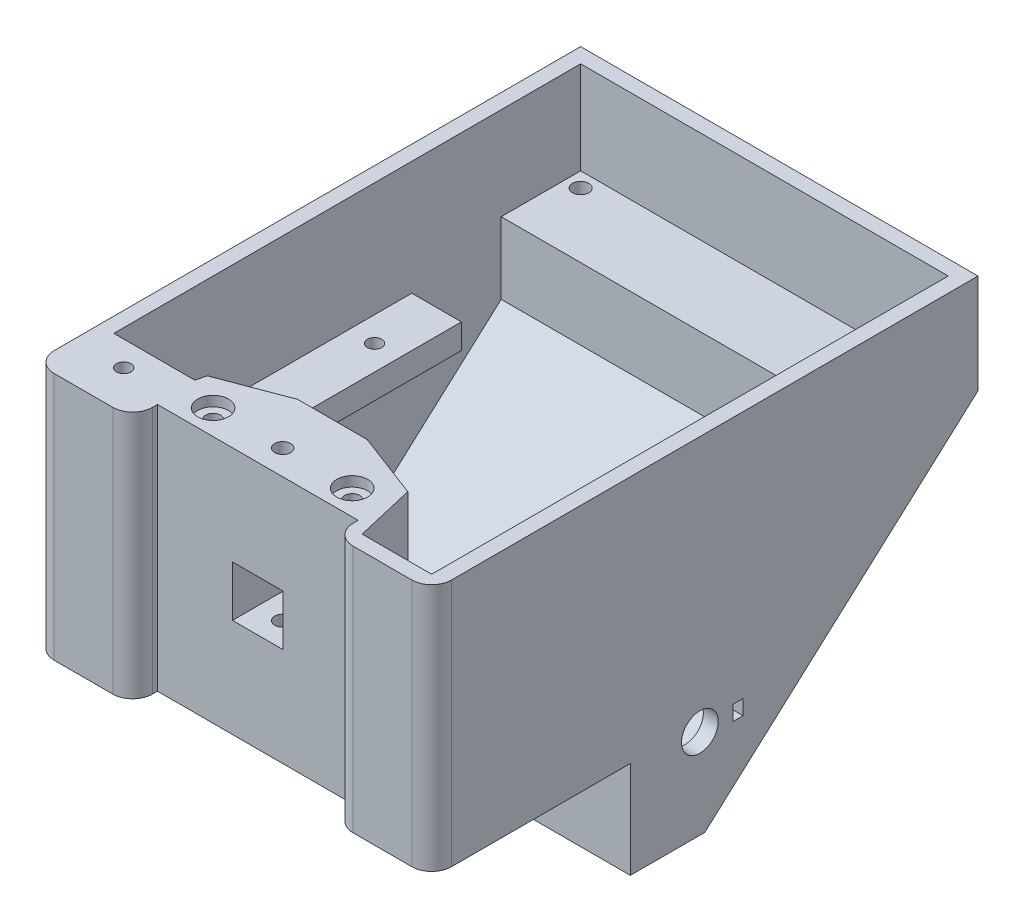
SolidWorks part; units mm, degrees
ref_plane "Спереди" through (0, 0, 0) normal (0, 0, 1) x (1, 0, 0)
ref_plane "Сверху" through (0, 0, 0) normal (0, 1, 0) x (1, 0, 0)
ref_plane "Справа" through (0, 0, 0) normal (1, 0, 0) x (0, 0, -1)
sketch "Sketch2" plane through (0, 0, 0) normal (1, 0, 0) x (0, 0, -1)
  line L0 (-27.3205, 20.9982) -> (-27.3205, -29.0018)
  line L1 (-27.3205, -29.0018) -> (12.6795, -29.0018)
  line L2 (12.6795, -29.0018) -> (12.6795, -48.5114)
  line L3 (12.6795, -48.5114) -> (27.6795, -48.5114)
  line L4 (82.6795, 20.9982) -> (82.6795, 0.9982)
  line L5 (82.6795, 20.9982) -> (-27.3205, 20.9982)
  line L6 (82.6795, 0.9982) -> (27.6795, -48.5114)
  dimension "D1" = 110
  dimension "D2" = 50
  dimension "D3" = 40
  dimension "D4" = 15
  dimension "D5" = 20
extrude "Boss-Extrude1" add sketch "Sketch2" along normal blind 80
shell "Shell1" thickness 3 removed face at (40, 20.9982, -27.6795)
sketch "Sketch3" plane through (0, 0, 24.3205) normal (0, 0, -1) x (-1, 0, 0)
  line L0 (-40, 20.9982) -> (-40, -26.0018) construction
  line L3 (-77, 20.9982) -> (-3, 20.9982) construction
  line L4 (-77, -26.0018) -> (-3, -26.0018) construction
  line L6 (-17, 20.9982) -> (-63, 20.9982)
  line L7 (-17, 20.9982) -> (-17, -26.0018)
  line L8 (-17, -26.0018) -> (-63, -26.0018)
  line L9 (-63, 20.9982) -> (-63, -26.0018)
  line L10 (-17, 20.9982) -> (-63, -26.0018) construction
  line L11 (-17, -26.0018) -> (-63, 20.9982) construction
  point P6 (-40, -2.5018)
  dimension "D1" = 46
extrude "Boss-Extrude2" add sketch "Sketch3" along normal blind 17
sketch "Sketch4" plane through (0, 0, 27.3205) normal (0, 0, 1) x (1, 0, 0)
  line L0 (0, 20.9982) -> (80, -29.0018) construction
  line L2 (45.1, -9.1018) -> (34.9, -9.1018)
  line L3 (45.1, -9.1018) -> (45.1, 1.0982)
  line L4 (45.1, 1.0982) -> (34.9, 1.0982)
  line L5 (34.9, -9.1018) -> (34.9, 1.0982)
  line L6 (45.1, -9.1018) -> (34.9, 1.0982) construction
  line L7 (45.1, 1.0982) -> (34.9, -9.1018) construction
  point P4 (40, -4.0018)
  dimension "D1" = 10.2
extrude "Cut-Extrude1" cut sketch "Sketch4" against normal up to surface (20 mm away) up to face at (40, -2.5018, 7.3205)
sketch "Sketch6" plane through (0, -29.0018, 0) normal (0, -1, 0) x (1, 0, 0)
  line L0 (40, 27.3205) -> (40, -12.6795) construction
  line L1 (47.5, -5.4795) -> (32.5, -5.4795)
  line L2 (47.5, -5.4795) -> (47.5, 7.3205)
  line L3 (47.5, 7.3205) -> (32.5, 7.3205)
  line L4 (32.5, -5.4795) -> (32.5, 7.3205)
  line L5 (47.5, -5.4795) -> (32.5, 7.3205) construction
  line L6 (47.5, 7.3205) -> (32.5, -5.4795) construction
  line L7 (80, -12.6795) -> (0, -12.6795) construction
  line L9 (80, 27.3205) -> (0, 27.3205) construction
  point P0 (40, 0.9205)
  dimension "D1" = 15
  dimension "D2" = 12.8
  dimension "D4" = 20
extrude "Cut-Extrude2" cut sketch "Sketch6" against normal up to surface (3 mm away) up to face at (40, -26.0018, 10.0705)
sketch "Sketch7" plane through (0, 0, 27.3205) normal (0, 0, 1) x (1, 0, 0)
  line L0 (40, 20.9982) -> (40, -29.0018) construction
  line L1 (80, 20.9982) -> (0, 20.9982) construction
  line L2 (80, -29.0018) -> (0, -29.0018) construction
  line L4 (60.2, -29.0018) -> (19.8, -29.0018)
  line L5 (60.2, -29.0018) -> (60.2, 20.9982)
  line L6 (60.2, 20.9982) -> (19.8, 20.9982)
  line L7 (19.8, -29.0018) -> (19.8, 20.9982)
  line L8 (60.2, -29.0018) -> (19.8, 20.9982) construction
  line L9 (60.2, 20.9982) -> (19.8, -29.0018) construction
  point P6 (40, -4.0018)
  dimension "D1" = 40.4
extrude "Cut-Extrude3" cut sketch "Sketch7" against normal blind 5
fillet "Fillet1" radius 4 4 edges at (19.8, -4.0018, 27.3205) (60.2, -4.0018, 27.3205) (80, -4.0018, 27.3205) (0, -4.0018, 27.3205)
sketch "Sketch12" plane through (0, 20.9982, 0) normal (0, 1, 0) x (1, 0, 0)
  line L0 (19.8, -22.3205) -> (19.8, -12.3205) construction
  line L1 (19.8, -12.3205) -> (60.2, -12.3205) construction
  line L2 (60.2, -12.3205) -> (60.2, -22.3205) construction
  line L3 (33, -7.3205) -> (19.8, -12.3205)
  line L4 (17, -7.3205) -> (63, -7.3205) construction
  line L5 (19.8, -12.3205) -> (17, -24.3205)
  line L6 (17, -24.3205) -> (17, -7.3205)
  line L7 (17, -7.3205) -> (33, -7.3205)
  line L8 (47, -7.3205) -> (63, -7.3205)
  line L9 (63, -7.3205) -> (63, -24.3205)
  line L10 (63, -24.3205) -> (60.2, -12.3205)
  line L11 (60.2, -12.3205) -> (47, -7.3205)
  dimension "D1" = 10
  dimension "D2" = 16
extrude "Cut-Extrude7" cut sketch "Sketch12" against normal up to surface (47 mm away) up to face at (40, -26.0018, 7.0205)
sketch "Sketch13" plane through (0, 20.9982, 0) normal (0, 1, 0) x (1, 0, 0)
  line L0 (19.8, -22.3205) -> (19.8, -12.3205) construction
  line L1 (19.8, -12.3205) -> (60.2, -12.3205) construction
  line L2 (60.2, -12.3205) -> (60.2, -22.3205) construction
  line L3 (60.2, -17.3205) -> (19.8, -17.3205) construction
  circle A0 centre (26, -17.3205) radius 1.5
  circle A1 centre (54, -17.3205) radius 1.5
  point P14 (40, -17.3205)
  dimension "D1" = 3
  dimension "D2" = 28
  dimension "D3" = 14
  dimension "D4" = 6.2
extrude "Cut-Extrude8" cut sketch "Sketch13" against normal blind 25
sketch "Sketch14" plane through (0, 20.9982, 0) normal (0, 1, 0) x (1, 0, 0)
  circle A0 centre (26, -17.3205) radius 3.1
  circle A1 centre (54, -17.3205) radius 3.1
  dimension "D1" = 6.2
extrude "Cut-Extrude9" cut sketch "Sketch14" against normal blind 2
sketch "Sketch17" plane through (77, 0, 0) normal (-1, 0, 0) x (0, 0, 1)
  line L0 (-45.6795, -2.0018) -> (-0.6795, -2.0018)
  line L1 (-0.6795, -2.0018) -> (-0.6795, -7.0018)
  line L2 (-0.6795, -7.0018) -> (-45.6795, -7.0018)
  line L3 (-45.6795, -7.0018) -> (-45.6795, -2.0018)
  line L4 (-79.6795, 20.9982) -> (24.3205, 20.9982) construction
  line L5 (-79.6795, 2.3342) -> (-79.6795, 20.9982) construction
  dimension "D1" = 45
  dimension "D2" = 5
  dimension "D3" = 23
  dimension "D4" = 34
extrude "Boss-Extrude5" add sketch "Sketch17" along normal up to surface (74 mm away) up to face at (3, -14.0994, -24.0865)
sketch "Sketch18" plane through (0, -2.0018, 0) normal (0, 1, 0) x (1, 0, 0)
  line L0 (40, 0.6795) -> (40, 45.6795) construction
  line L1 (3, 0.6795) -> (77, 0.6795) construction
  line L2 (3, 45.6795) -> (77, 45.6795) construction
  line L3 (77, 0.6795) -> (77, 45.6795) construction
  line L4 (13, 0.6795) -> (67, 0.6795)
  line L5 (13, 0.6795) -> (13, 45.6795)
  line L6 (13, 45.6795) -> (67, 45.6795)
  line L7 (67, 0.6795) -> (67, 45.6795)
  line L8 (13, 0.6795) -> (67, 45.6795) construction
  line L9 (13, 45.6795) -> (67, 0.6795) construction
  point P6 (40, 23.1795)
  dimension "D1" = 10
extrude "Cut-Extrude10" cut sketch "Sketch18" against normal up to next
sketch "Sketch19" plane through (0, -2.0018, 0) normal (0, 1, 0) x (1, 0, 0)
  line L0 (72, 45.6795) -> (72, 0.6795) construction
  line L1 (67, 45.6795) -> (77, 45.6795) construction
  line L2 (67, 0.6795) -> (77, 0.6795) construction
  line L3 (8, 45.6795) -> (8, 0.6795) construction
  line L4 (3, 45.6795) -> (13, 45.6795) construction
  line L5 (3, 0.6795) -> (13, 0.6795) construction
  circle A0 centre (72, 37.1795) radius 1.45
  circle A1 centre (72, 6.1795) radius 1.45
  circle A2 centre (8, 33.1795) radius 1.45
  circle A3 centre (8, 6.1795) radius 1.45
  point P20 (72, 23.1795)
  point P21 (8, 23.1795)
  dimension "D1" = 2.9
  dimension "D2" = 14
  dimension "D3" = 17
  dimension "D4" = 17
  dimension "D5" = 10
extrude "Cut-Extrude11" cut sketch "Sketch19" against normal up to next
sketch "Sketch21" plane through (0, -26.0018, 0) normal (0, 1, 0) x (1, 0, 0)
  line L0 (3, -24.3205) -> (3, -14.3205)
  line L1 (3, -24.3205) -> (3, 15.6795) construction
  line L2 (3, -14.3205) -> (19.3333, -14.3205)
  line L3 (19.8, -12.3205) -> (17, -24.3205) construction
  line L4 (19.3333, -14.3205) -> (17, -24.3205)
  line L6 (3, -24.3205) -> (17, -24.3205)
  dimension "D1" = 10
extrude "Boss-Extrude6" add sketch "Sketch21" along normal up to surface (47 mm away) up to face at (54, 20.9982, 20.4205)
sketch "Sketch22" plane through (0, 20.9982, 0) normal (0, 1, 0) x (1, 0, 0)
  line L0 (0, 82.6795) -> (0, -23.3205) construction
  line L1 (15.8, -27.3205) -> (4, -27.3205) construction
  circle A0 centre (10, -19.3205) radius 1.45
  dimension "D1" = 2.9
  dimension "D2" = 10
  dimension "D3" = 8
extrude "Cut-Extrude12" cut sketch "Sketch22" against normal through all
sketch "Sketch24" plane through (80, 0, 0) normal (1, 0, 0) x (0, 0, -1)
  line L0 (12.6795, -48.5114) -> (27.6795, -48.5114) construction
  line L1 (12.6795, -29.0018) -> (12.6795, -48.5114) construction
  line L2 (18.1795, -30.5114) -> (18.1795, -19.0114) construction
  line L3 (18.1795, -19.0114) -> (35.1795, -19.0114) construction
  line L4 (35.1795, -19.0114) -> (35.1795, -30.5114) construction
  line L5 (26.6795, -19.0114) -> (26.6795, -39.0114) construction
  line L6 (30.3795, -30.5114) -> (34.3795, -30.5114) construction
  line L8 (33.3795, -32.0114) -> (35.3795, -32.0114)
  line L9 (33.3795, -32.0114) -> (33.3795, -29.0114)
  line L10 (33.3795, -29.0114) -> (35.3795, -29.0114)
  line L11 (35.3795, -32.0114) -> (35.3795, -29.0114)
  line L12 (33.3795, -32.0114) -> (35.3795, -29.0114) construction
  line L13 (33.3795, -29.0114) -> (35.3795, -32.0114) construction
  circle A0 centre (26.6795, -30.5114) radius 3.7
  circle A1 centre (26.6795, -30.5114) radius 8.5 construction
  dimension "D1" = 7.4
  dimension "D2" = 17
  dimension "D3" = 18
  dimension "D4" = 14
  dimension "D5" = 20
  dimension "D6" = 4
  dimension "D7" = 2
  dimension "D8" = 3
extrude "Cut-Extrude13" cut sketch "Sketch24" against normal up to next
sketch "Sketch26" plane through (3, 0, 0) normal (1, 0, 0) x (0, 0, -1)
  line L0 (79.6795, 2.3342) -> (63.6795, 2.3342)
  line L1 (63.6795, 2.3342) -> (63.6795, -12.0686)
  line L2 (26.5281, -45.5114) -> (79.6795, 2.3342) construction
  line L3 (63.6795, -12.0686) -> (79.6795, 2.3342)
  dimension "D1" = 16
extrude "Boss-Extrude7" add sketch "Sketch26" along normal up to surface (74 mm away) up to face at (77, -30.5114, -34.3795)
sketch "Sketch27" plane through (0, 2.3342, 0) normal (0, 1, 0) x (1, 0, 0)
  line L0 (3, 76.6795) -> (77, 76.6795) construction
  line L1 (3, 79.6795) -> (3, 63.6795) construction
  line L2 (77, 79.6795) -> (77, 63.6795) construction
  line L3 (80, 82.6795) -> (0, 82.6795) construction
  circle A0 centre (6, 76.6795) radius 1.65
  circle A1 centre (74, 76.6795) radius 1.65
  point P10 (40, 76.6795)
  dimension "D1" = 3.3
  dimension "D2" = 68
  dimension "D3" = 34
  dimension "D4" = 6
extrude "Cut-Extrude14" cut sketch "Sketch27" against normal blind 10
sketch "Sketch28" plane through (0, 2.3342, 0) normal (0, 1, 0) x (1, 0, 0)
  line L1 (74, 79.9295) -> (71.1854, 78.3045)
  line L2 (71.1854, 78.3045) -> (71.1854, 75.0545)
  line L3 (71.1854, 75.0545) -> (74, 73.4295)
  line L4 (74, 73.4295) -> (76.8146, 75.0545)
  line L5 (76.8146, 75.0545) -> (76.8146, 78.3045)
  line L6 (76.8146, 78.3045) -> (74, 79.9295)
  line L7 (6, 73.4295) -> (8.8146, 75.0545)
  line L8 (8.8146, 75.0545) -> (8.8146, 78.3045)
  line L9 (8.8146, 78.3045) -> (6, 79.9295)
  line L10 (6, 79.9295) -> (3.1854, 78.3045)
  line L11 (3.1854, 78.3045) -> (3.1854, 75.0545)
  line L12 (3.1854, 75.0545) -> (6, 73.4295)
  circle A0 centre (74, 76.6795) radius 3.25 construction
  circle A1 centre (6, 76.6795) radius 3.25 construction
  dimension "D1" = 6.5
extrude "Cut-Extrude15" cut sketch "Sketch28" against normal blind 32 from offset 3 offset against normal yes
sketch "Sketch29" plane through (0, -29.0018, 0) normal (0, -1, 0) x (1, 0, 0)
  line L0 (0, 23.3205) -> (0, -12.6795) construction
  line L1 (7.1854, 17.6955) -> (10, 16.0705)
  line L2 (10, 16.0705) -> (12.8146, 17.6955)
  line L3 (12.8146, 17.6955) -> (12.8146, 20.9455)
  line L4 (12.8146, 20.9455) -> (10, 22.5705)
  line L5 (10, 22.5705) -> (7.1854, 20.9455)
  line L6 (7.1854, 20.9455) -> (7.1854, 17.6955)
  circle A0 centre (10, 19.3205) radius 3.25 construction
  dimension "D1" = 6.5
extrude "Cut-Extrude16" cut sketch "Sketch29" against normal blind 30
sketch "Sketch30" plane through (0, -26.0018, 0) normal (0, 1, 0) x (1, 0, 0)
  line L0 (77, -24.3205) -> (63, -24.3205)
  line L1 (63, -24.3205) -> (60.2, -12.3205)
  line L2 (63, -24.3205) -> (60.2, -12.3205) construction
  line L3 (60.2, -12.3205) -> (77, -12.3205)
  line L4 (77, -24.3205) -> (77, 15.6795) construction
  line L5 (77, -12.3205) -> (77, -24.3205)
  dimension "D1" = 12
extrude "Boss-Extrude8" add sketch "Sketch30" along normal blind 20
sketch "Sketch31" plane through (0, -6.0018, 0) normal (0, 1, 0) x (1, 0, 0)
  line L0 (76, -27.3205) -> (64.2, -27.3205) construction
  line L1 (80, -23.3205) -> (80, 12.6795) construction
  circle A0 centre (72, -21.3205) radius 1.5
  dimension "D3" = 3
  dimension "D1" = 6
  dimension "D2" = 8
extrude "Cut-Extrude17" cut sketch "Sketch31" against normal through all
sketch "Sketch32" plane through (0, -29.0018, 0) normal (0, -1, 0) x (1, 0, 0)
  line L1 (72, 24.5705) -> (69.1854, 22.9455)
  line L2 (69.1854, 22.9455) -> (69.1854, 19.6955)
  line L3 (69.1854, 19.6955) -> (72, 18.0705)
  line L4 (72, 18.0705) -> (74.8146, 19.6955)
  line L5 (74.8146, 19.6955) -> (74.8146, 22.9455)
  line L6 (74.8146, 22.9455) -> (72, 24.5705)
  circle A0 centre (72, 21.3205) radius 3.25 construction
  dimension "D1" = 6.5
extrude "Cut-Extrude18" cut sketch "Sketch32" against normal blind 15
sketch "Sketch33" plane through (0, -2.0018, 0) normal (0, 1, 0) x (1, 0, 0)
  line L0 (67, 40.6795) -> (77, 40.6795)
  line L1 (67, 0.6795) -> (67, 45.6795) construction
  line L2 (77, 0.6795) -> (77, 45.6795) construction
  line L3 (77, 40.6795) -> (77, 45.6795)
  line L4 (77, 45.6795) -> (67, 45.6795)
  line L5 (67, 45.6795) -> (67, 40.6795)
  dimension "D1" = 5
extrude "Cut-Extrude19" cut sketch "Sketch33" against normal up to next
sketch "Sketch34" plane through (0, 20.9982, 0) normal (0, 1, 0) x (1, 0, 0)
  line L0 (54, -17.3205) -> (26, -17.3205) construction
  circle A0 centre (40, -17.3205) radius 1.6
  dimension "D1" = 3.2
extrude "Cut-Extrude20" cut sketch "Sketch34" against normal through all
sketch "Sketch36" plane through (0, -29.0018, 0) normal (0, -1, 0) x (1, 0, 0)
  line L1 (38.375, 20.1351) -> (36.75, 17.3205)
  line L2 (36.75, 17.3205) -> (38.375, 14.5059)
  line L3 (38.375, 14.5059) -> (41.625, 14.5059)
  line L4 (41.625, 14.5059) -> (43.25, 17.3205)
  line L5 (43.25, 17.3205) -> (41.625, 20.1351)
  line L6 (41.625, 20.1351) -> (38.375, 20.1351)
  circle A0 centre (40, 17.3205) radius 3.25 construction
  dimension "D1" = 6.5
extrude "Cut-Extrude22" cut sketch "Sketch36" against normal blind 14
sketch "Sketch37" plane through (80, 0, 0) normal (1, 0, 0) x (0, 0, -1)
  line L0 (-23.3205, -16.5114) -> (63.2281, -16.5114) construction
  line L1 (-23.3205, 20.9982) -> (-23.3205, -29.0018) construction
  line L2 (27.6795, -48.5114) -> (82.6795, 0.9982) construction
  line L3 (30.3795, -30.5114) -> (22.9795, -30.5114) construction
  circle A0 centre (-3.3205, -16.5114) radius 3.2
  circle A1 centre (26.6795, -30.5114) radius 3.7 construction
  point P14 (26.6795, -30.5114)
  dimension "D1" = 6.4
  dimension "D2" = 14
  dimension "D3" = 20
sketch "Sketch40" plane through (3, 0, 0) normal (1, 0, 0) x (0, 0, -1)
  line L0 (18.1795, -30.5114) -> (18.1795, -19.0114) construction
  line L1 (18.1795, -19.0114) -> (35.1795, -19.0114) construction
  line L2 (35.1795, -19.0114) -> (35.1795, -30.5114) construction
  line L3 (26.6795, -19.0114) -> (26.6795, -39.0114) construction
  line L4 (30.3795, -30.5114) -> (34.3795, -30.5114) construction
  line L5 (33.3795, -32.0114) -> (35.3795, -32.0114) construction
  line L6 (33.3795, -32.0114) -> (33.3795, -29.0114) construction
  line L7 (33.3795, -29.0114) -> (35.3795, -29.0114) construction
  line L8 (35.3795, -32.0114) -> (35.3795, -29.0114) construction
  line L9 (33.3795, -32.0114) -> (35.3795, -29.0114) construction
  line L10 (33.3795, -29.0114) -> (35.3795, -32.0114) construction
  line L13 (22.9795, -30.5114) -> (18.9795, -30.5114) construction
  line L14 (12.6795, -29.0018) -> (12.6795, -48.5114) construction
  line L15 (17.9795, -29.0114) -> (19.9795, -29.0114)
  line L16 (17.9795, -29.0114) -> (17.9795, -32.0114)
  line L17 (17.9795, -32.0114) -> (19.9795, -32.0114)
  line L18 (19.9795, -29.0114) -> (19.9795, -32.0114)
  line L19 (17.9795, -29.0114) -> (19.9795, -32.0114) construction
  line L20 (17.9795, -32.0114) -> (19.9795, -29.0114) construction
  line L21 (12.6795, -48.5114) -> (27.6795, -48.5114) construction
  circle A0 centre (26.6795, -30.5114) radius 3.7
  circle A1 centre (26.6795, -30.5114) radius 8.5 construction
  dimension "D4" = 17
  dimension "D5" = 17
  dimension "D11" = 7.4
  dimension "D1" = 3
  dimension "D2" = 2
  dimension "D3" = 4
  dimension "D6" = 2
  dimension "D7" = 3
  dimension "D8" = 4
  dimension "D9" = 14
  dimension "D10" = 18
extrude "Cut-Extrude24" cut sketch "Sketch40" against normal up to next
